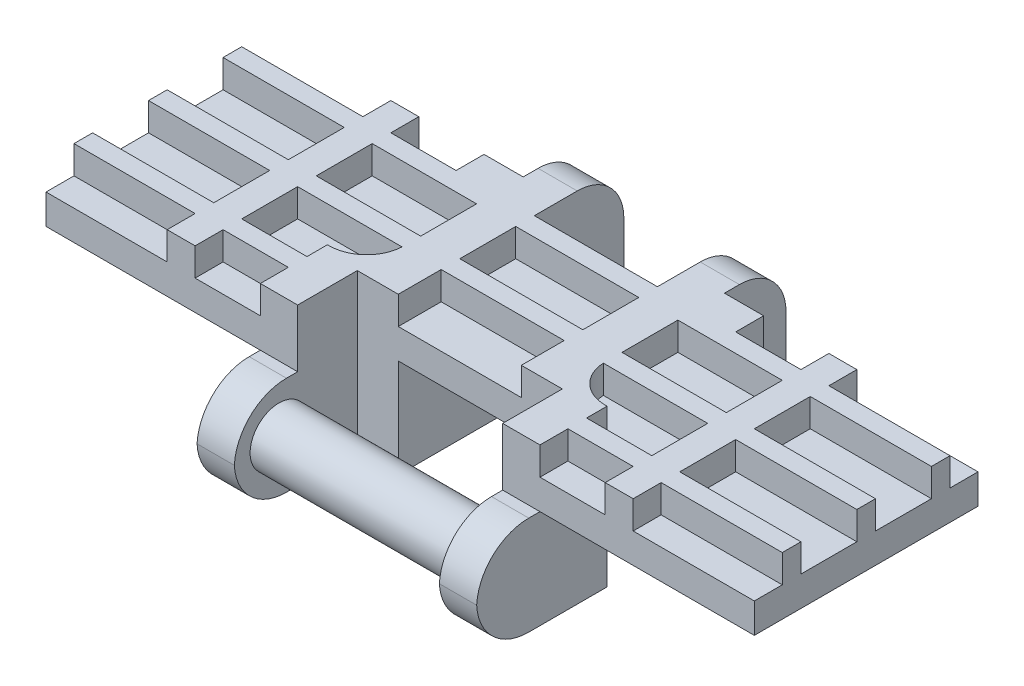
SolidWorks part; units mm, degrees
ref_plane "前视基准面" through (0, 0, 0) normal (0, 0, 1) x (1, 0, 0)
ref_plane "上视基准面" through (0, 0, 0) normal (0, 1, 0) x (1, 0, 0)
ref_plane "右视基准面" through (0, 0, 0) normal (1, 0, 0) x (0, 0, -1)
other "Configuration Table"
sketch "草图1" plane through (0, 0, 0) normal (0, 1, 0) x (1, 0, 0)
  line L1 (-19, -6) -> (19, -6)
  line L2 (-19, -6) -> (-19, 6)
  line L3 (-19, 6) -> (19, 6)
  line L4 (19, -6) -> (19, 6)
  line L5 (-19, -6) -> (19, 6) construction
  line L6 (-19, 6) -> (19, -6) construction
  line L13 (-19, 4.5) -> (19, 4.5)
  line L14 (-19, 4.5) -> (-19, 3.5)
  line L15 (-19, 3.5) -> (19, 3.5)
  line L16 (19, 4.5) -> (19, 3.5)
  line L17 (-19, 0.5) -> (19, 0.5)
  line L18 (-19, 0.5) -> (-19, -0.5)
  line L19 (-19, -0.5) -> (19, -0.5)
  line L20 (19, 0.5) -> (19, -0.5)
  line L21 (-19, -3.5) -> (19, -3.5)
  line L22 (-19, -3.5) -> (-19, -4.5)
  line L23 (-19, -4.5) -> (19, -4.5)
  line L24 (19, -3.5) -> (19, -4.5)
  line L25 (-12.5, 6) -> (-11, 6)
  line L26 (-12.5, 6) -> (-12.5, -6)
  line L27 (-12.5, -6) -> (-11, -6)
  line L28 (-11, 6) -> (-11, -6)
  line L29 (12.5, 6) -> (11, 6)
  line L30 (12.5, 6) -> (12.5, -6)
  line L31 (12.5, -6) -> (11, -6)
  line L32 (11, 6) -> (11, -6)
  point P0 (0, 0)
  point P6 (0, 0)
  dimension "D1" = 38
  dimension "D2" = 12
  dimension "D3" = 11
  dimension "D4" = 11
  dimension "D5" = 1
  dimension "D6" = 1.5
  dimension "D7" = 1.5
  dimension "D8" = 5.5
  dimension "D9" = 1.5
extrude "凸台-拉伸1" add sketch "草图1" along normal blind 1.6 contours L2 L3 L4 L1
extrude "凸台-拉伸2" add sketch "草图1<3>" along normal blind 1.5 from surface contours L13 L16 L15 L14 | L17 L20 L19 L18 | L21 L24 L23 L22 | L26 L27 L28 L25 | L30 L31 L32 L29 starting at face at (0, 1.6, 0)
sketch "草图1<3>" plane through (0, 0, 0) normal (0, 1, 0) x (1, 0, 0) same geometry as "草图1"
sketch "草图2" plane through (0, 0, 0) normal (0, 1, 0) x (1, 0, 0)
  line L0 (0, 0) -> (0, -13.8005) construction
  line L1 (-5.4, 9.3) -> (5.4, 9.3)
  line L2 (-5.4, 9.3) -> (-5.4, -2.8)
  line L3 (-5.4, -2.8) -> (5.4, -2.8)
  line L4 (5.4, 9.3) -> (5.4, -2.8)
  line L5 (-7.5, -2.8) -> (7.5, -2.8)
  line L6 (11, 4.5) -> (-11, 4.5) construction
  line L7 (-7.5, 6) -> (-5.4, 6)
  line L8 (-3.3, 9.3) -> (3.3, 9.3)
  line L9 (-3.3, 9.3) -> (-3.3, -2.8)
  line L10 (-3.3, -2.8) -> (3.3, -2.8)
  line L11 (3.3, 9.3) -> (3.3, -2.8)
  line L16 (-11, -6) -> (11, -6) construction
  line L17 (-11, 6) -> (11, 6) construction
  line L18 (-5.5, -2.4) -> (-5.5, -9.4)
  line L19 (-7.5, -2.4) -> (7.5, -2.4)
  line L20 (-7.5, -2.4) -> (-7.5, -9.4)
  line L21 (-7.5, -9.4) -> (7.5, -9.4)
  line L22 (7.5, -2.4) -> (7.5, -9.4)
  line L23 (5.5, -2.4) -> (5.5, -9.4)
  line L24 (-7.5, 6) -> (-7.5, 4.5)
  line L25 (-7.5, 4.5) -> (-5.4, 4.5)
  line L26 (-5.4, 6) -> (-5.4, 4.5)
  line L27 (7.5, 6) -> (5.4, 6)
  line L28 (7.5, 6) -> (7.5, 4.5)
  line L29 (7.5, 4.5) -> (5.4, 4.5)
  line L30 (5.4, 6) -> (5.4, 4.5)
  point P5 (0, -2.8)
  point P15 (0, 9.3)
  point P20 (0, -9.4)
  dimension "D1" = 10.8
  dimension "D2" = 3.2
  dimension "D3" = 6.6
  dimension "D4" = 3.3
  dimension "D5" = 15
  dimension "D6" = 2
  dimension "D7" = 2
  dimension "D8" = 3.4
  dimension "D9" = 7
extrude "凸台-拉伸3" add sketch "草图2" against normal blind 8.4 from surface contours L1 L11 L3 L4 | L9 L1 L2 L3 | L20 L21 L18 L19 | L19 L23 L21 L22 | L19 L18 L5 L2 | L19 L20 L5 L18 | L19 L2 L3 L9 | L19 L11 L3 L4 | L23 L19 L4 L5 | L19 L23 L5 L22 region at (-4.35, 0, -3.45) region at (4.35, 0, -3.45) region at (-4.35, 0, 2.6) region at (4.35, 0, 2.6) region at (-5.45, 0, 2.6) region at (5.45, 0, 2.6) region at (-6.5, 0, 2.6) region at (6.5, 0, 2.6) region at (-6.5, 0, 6.1) region at (6.5, 0, 6.1) starting at face at (0, 3.1, 0)
extrude "凸台-拉伸5" add sketch "草图2<4>" along normal up to surface (3.1 mm away) contours L27 L30 L29 L28 | L7 L26 L25 L24 up to face at (0, 3.1, -2)
sketch "草图2<4>" plane through (0, 0, 0) normal (0, 1, 0) x (1, 0, 0) same geometry as "草图2"
extrude "切除-拉伸1" cut sketch "草图2<3>" along normal through all contours L0 L5 L3 L18 L21 | L10 L0 L21 L23 L5 L3 region at (2.75, 0, 6.1) region at (-2.75, 0, 6.1)
sketch "草图2<3>" plane through (0, 0, 0) normal (0, 1, 0) x (1, 0, 0) same geometry as "草图2"
fillet "圆角1" radius 3 2 edges at (5.4, -2.65, 2.4) (-5.4, -2.65, 2.4)
sketch "草图3" plane through (-5.5, 0, 0) normal (1, 0, 0) x (0, 0, -1)
  line L2 (-7, -2.5) -> (5.58, -2.5)
  line L3 (2.8, -4.1) -> (9.3, -4.1)
  line L4 (2.8, -4.1) -> (2.8, -5.3)
  line L5 (2.8, -5.3) -> (9.3, -5.3)
  line L6 (9.3, -4.1) -> (9.3, -5.3)
  line L7 (-9.4, -5.3) -> (-9.4, 3.1) construction
  line L8 (-6, 3.1) -> (-9.4, 3.1)
  line L9 (-6, 3.1) -> (-6, 0)
  line L10 (-6, 0) -> (-9.4, 0)
  line L11 (-9.4, 3.1) -> (-9.4, 0)
  circle A0 centre (-7, -2.5) radius 1.55
  circle A1 centre (5.58, -2.5) radius 1.7
  point P5 (0, 0)
  dimension "D1" = 3.1
  dimension "D3" = 3.4
  dimension "D7" = 7
  dimension "D2" = 2.5
  dimension "D4" = 1.2
  dimension "D5" = 6.5
  dimension "D6" = 12.58
extrude "凸台-拉伸4" add sketch "草图3" along normal up to next contours A0
extrude "切除-拉伸2" cut sketch "草图3<3>" along normal through all both and the other way through all contours L3 L6 L5 L4 | A1 | L11 L10 L9 L8
sketch "草图3<3>" plane through (-5.5, 0, 0) normal (1, 0, 0) x (0, 0, -1) same geometry as "草图3"
fillet "圆角2" radius 2.8 4 edges at (6.5, -5.3, 9.4) (-6.5, -5.3, 9.4) (-6.5, 0, 9.4) (6.5, 0, 9.4)
fillet "圆角3" radius 2.5 2 edges at (-4.35, 3.1, -9.3) (4.35, 3.1, -9.3)
fillet "圆角4" radius 1 2 edges at (-4.35, -4.1, -9.3) (4.35, -4.1, -9.3)
fillet "圆角5" radius 0.3 4 edges at (-4.35, -4.1, -6.1545) (4.35, -4.1, -6.1545) (4.35, -4.1, -5.0055) (-4.35, -4.1, -5.0055)
fillet "圆角6" radius 2 2 edges at (5.4, 2.35, 2.4) (-5.4, 2.35, 2.4)
